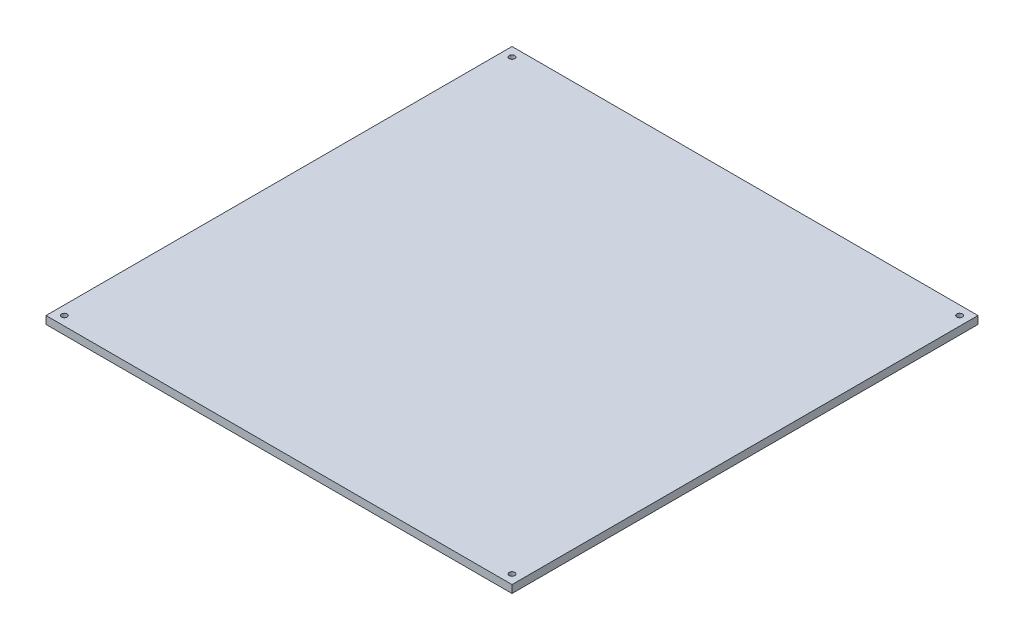
SolidWorks part; units mm, degrees
ref_plane "Front Plane" through (0, 0, 0) normal (0, 0, 1) x (1, 0, 0)
ref_plane "Top Plane" through (0, 0, 0) normal (0, 1, 0) x (1, 0, 0)
ref_plane "Right Plane" through (0, 0, 0) normal (1, 0, 0) x (0, 0, -1)
sketch "Sketch1" plane through (0, 0, 0) normal (0, 1, 0) x (1, 0, 0)
  line L1 (-150, -150) -> (150, -150)
  line L2 (-150, -150) -> (-150, 150)
  line L3 (-150, 150) -> (150, 150)
  line L4 (150, -150) -> (150, 150)
  line L5 (-150, -150) -> (150, 150) construction
  line L6 (-150, 150) -> (150, -150) construction
  point P0 (0, 0)
  dimension "D1" = 300
  dimension "D2" = 300
extrude "Boss-Extrude1" add sketch "Sketch1" along normal blind 5
sketch "Sketch2" plane through (0, 0, 0) normal (0, -1, 0) x (1, 0, 0)
  line L0 (150, 150) -> (-150, -150) construction
  line L1 (150, -150) -> (-150, 150) construction
  line L2 (-150, 150) -> (150, 150) construction
  point P8 (144.1, 144.1)
  point P9 (-144.1, 144.1)
  point P10 (-144.1, -144.1)
  point P11 (144.1, -144.1)
  dimension "D1" = 5.9
hole_wizard "CSK for M3 Countersunk Flat Head Screw1" positions "3DSketch1" profile "Sketch3" countersink size "M3" standard "ISO" end condition through all
sketch3d "3DSketch1"
  point P0 (144.1, 0, 144.1)
  point P3 (-144.1, 0, 144.1)
  point P6 (-144.1, 0, -144.1)
  point P9 (144.1, 0, -144.1)
sketch "Sketch3" plane through (144.1, 0, 144.1) normal (1, 0, 0) x (0, 0, -1)
  line L0 (0, 0) -> (0, 5)
  line L1 (0, 5) -> (1.8, 5)
  line L2 (1.8, 5) -> (1.8, 1.35)
  line L3 (1.8, 1.35) -> (3.15, 0)
  line L5 (3.15, 0) -> (0, 0)
  line L6 (-1.8, 1.35) -> (-3.15, 0) construction
  line L11 (0, -6.35) -> (0, 107.95) construction
  dimension "Thru Hole Dia." = 3.6
  dimension "Thru Hole Depth" = 5
  dimension "Near C'Sink Dia." = 6.3
  dimension "Near C'Sink Angle" = 90
sketch "Sketch4" plane through (0, 0, 0) normal (0, -1, 0) x (1, 0, 0)
  point P0 (-144.1, -144.1)
  point P1 (-144.1, 144.1)
